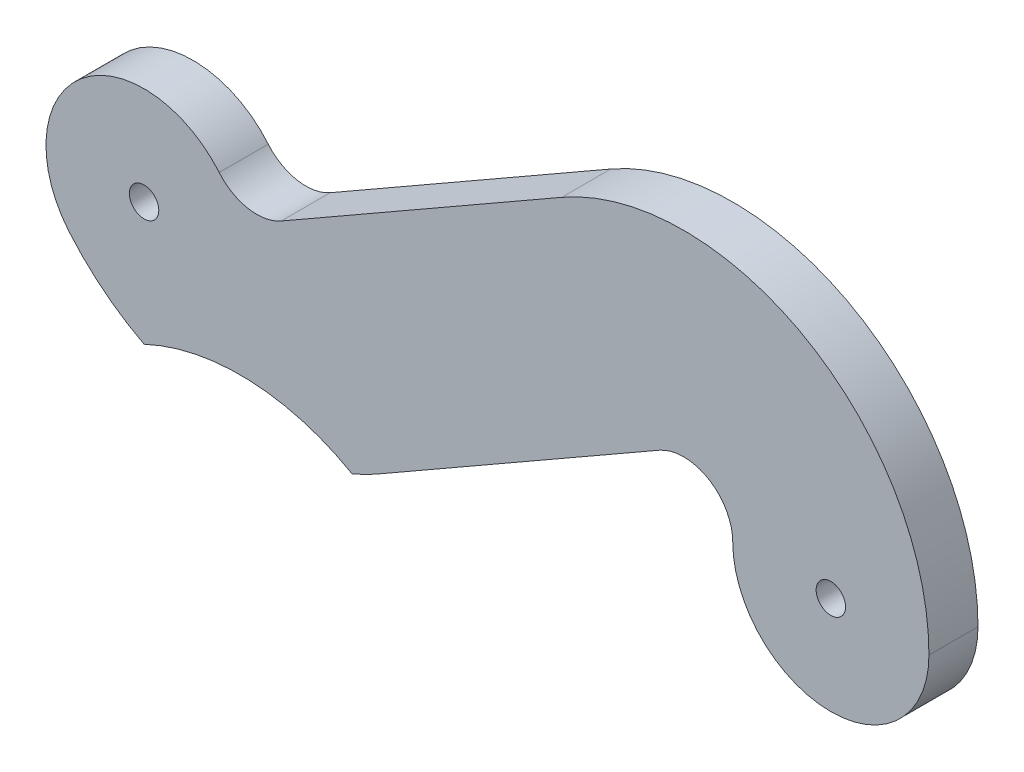
SolidWorks part; units mm, degrees
ref_plane "Plan de face" through (0, 0, 0) normal (0, 0, 1) x (1, 0, 0)
ref_plane "Plan de dessus" through (0, 0, 0) normal (0, 1, 0) x (1, 0, 0)
ref_plane "Plan de droite" through (0, 0, 0) normal (1, 0, 0) x (0, 0, -1)
sketch "Esquisse1" plane through (0, 0, 0) normal (0, 0, 1) x (1, 0, 0)
  line L0 (0, 0) -> (70, 0) construction
  line L1 (0, 0) -> (0, 15) construction
  line L2 (0, 0) -> (11.4907, 9.6418) construction
  line L3 (70, -15) -> (70, 0) construction
  line L4 (70, 0) -> (55, 0) construction
  line L5 (13.9769, 5.3038) -> (42.569, 21.6903)
  line L6 (23.9217, -12.0485) -> (52.5138, 4.3381)
  arc A0 (11.4907, 9.6418) -> (0, 15) centre (0, 0) ccw construction
  arc A1 (15.3209, 12.8558) -> (0, 20) centre (0, 0) ccw construction
  circle A2 centre (70, 0) radius 1.5
  circle A3 centre (0, 0) radius 1.5
  arc A4 (7.6604, 6.4279) -> (0, 10) centre (0, 0) ccw construction
  arc A5 (7.6604, 6.4279) -> (15.3209, 12.8558) centre (11.4907, 9.6418) ccw construction
  arc A6 (0, 20) -> (0, 10) centre (0, 15) ccw construction
  arc A7 (55, 0) -> (70, -15) centre (70, 0) ccw construction
  arc A8 (50, 0) -> (70, -20) centre (70, 0) ccw construction
  arc A9 (60, 0) -> (70, -10) centre (70, 0) ccw construction
  arc A10 (60, 0) -> (50, 0) centre (55, 0) ccw construction
  arc A11 (70, -20) -> (70, -10) centre (70, -15) ccw construction
  arc A12 (7.6604, 6.4279) -> (-7.6604, -6.4279) centre (0, 0) ccw
  arc A13 (60, 0) -> (80, 0) centre (70, 0) ccw
  arc A14 (7.6604, 6.4279) -> (13.9769, 5.3038) centre (11.4907, 9.6418) ccw
  arc A15 (60, 0) -> (52.5138, 4.3381) centre (55, 0) ccw
  arc A16 (-7.6604, -6.4279) -> (23.9217, -12.0485) centre (11.4907, 9.6418) ccw
  arc A17 (80, 0) -> (42.569, 21.6903) centre (55, 0) ccw
  point P6 (6.3393, 13.5946)
  point P15 (59.3934, -10.6066)
  dimension "D1" = 3
  dimension "D2" = 70
  dimension "D3" = 15
  dimension "D6" = 50
  dimension "D7" = 90
  dimension "D8" = 5
  dimension "D4" = 90
extrude "Boss.-Extru.1" add sketch "Esquisse1" along normal blind 5
sketch "Esquisse2" plane through (0, 0, 5) normal (0, 0, 1) x (1, 0, 0)
  arc A0 (0, -12.561) -> (21.1946, -13.398) centre (9.7934, -33.3359) cw
  arc A1 (-7.6604, -6.4279) -> (23.9217, -12.0485) centre (11.4907, 9.6418) ccw construction
  arc A2 (0, -12.561) -> (21.1946, -13.398) centre (11.4907, 9.6418) ccw
extrude "Enlèv. mat.-Extru.1" cut sketch "Esquisse2" against normal blind 10
